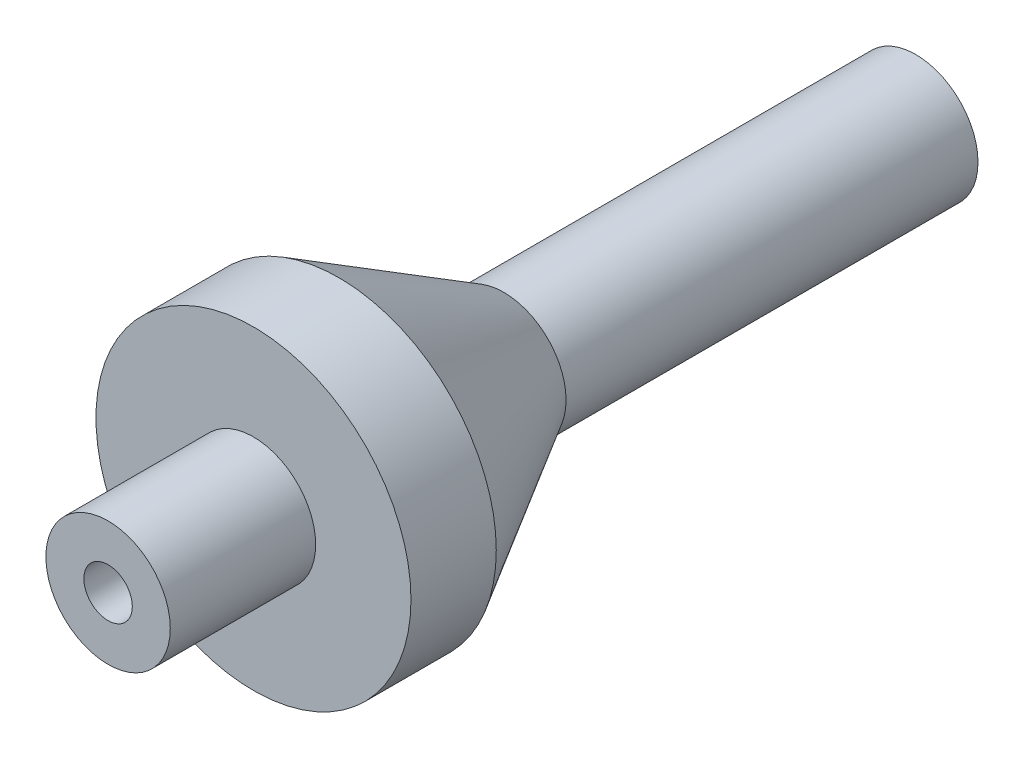
SolidWorks part; units mm, degrees
ref_plane "Top Plane" through (0, 0, 0) normal (0, 0, 1) x (1, 0, 0)
ref_plane "Right Plane" through (0, 0, 0) normal (0, 1, 0) x (1, 0, 0)
ref_plane "Front Plane" through (0, 0, 0) normal (1, 0, 0) x (0, 0, -1)
sketch "Sketch2" plane through (0, 0, 0) normal (0, 1, 0) x (1, 0, 0)
  line L0 (0, 0) -> (0, 50) construction
  line L1 (1.5, 0) -> (3.85, 0)
  line L2 (1.5, 0) -> (1.5, 50)
  line L3 (1.5, 50) -> (3.85, 50)
  line L4 (3.85, 50) -> (3.85, 14)
  line L5 (3.85, 14) -> (9.75, 14)
  line L6 (9.75, 14) -> (9.75, 9)
  line L7 (9.75, 9) -> (3.85, 9)
  line L8 (3.85, 9) -> (3.85, 0)
  line L9 (3.85, 0) -> (9.75, 0) construction
  line L10 (0, 50) -> (1.5, 50) construction
  dimension "D1" = 9.75
  dimension "D2" = 1.5
  dimension "D3" = 50
  dimension "D4" = 3.85
  dimension "D5" = 9
  dimension "D6" = 5
revolve "Revolve1" add sketch "Sketch2" angle 360 about L0
chamfer "Chamfer1" distance 10.5 angle 30 1 edges at (3.85, 0, -14) first distance on face at (3.85, 0, -50)
